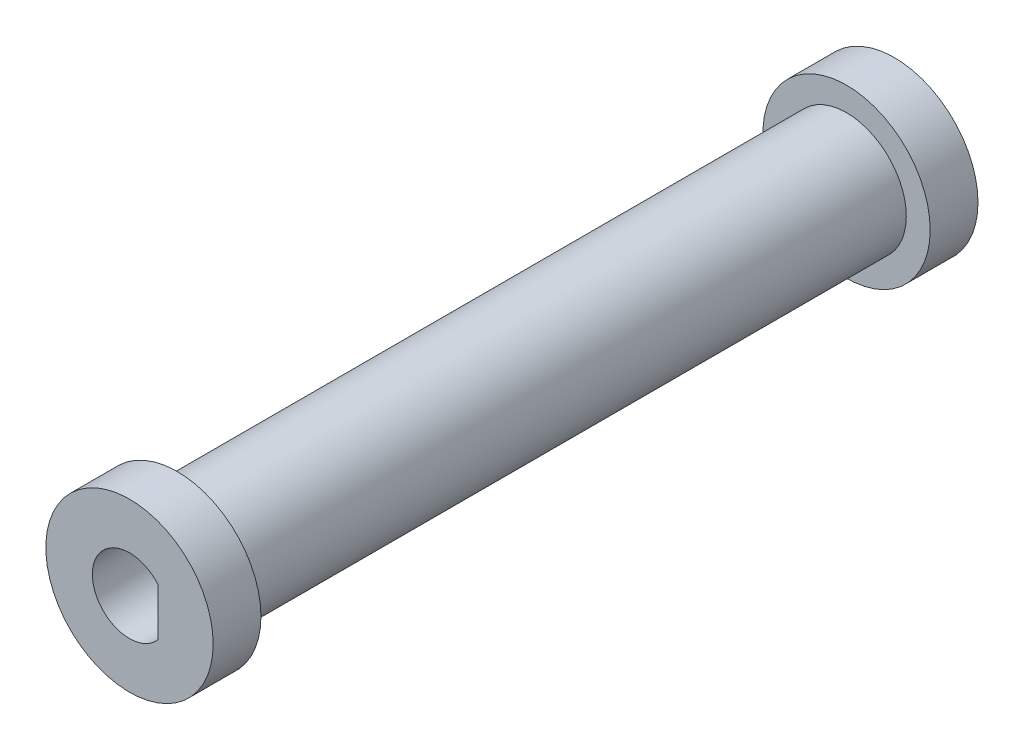
SolidWorks part; units mm, degrees
material "ABS"
ref_plane "Front Plane" through (0, 0, 0) normal (0, 0, 1) x (1, 0, 0)
ref_plane "Top Plane" through (0, 0, 0) normal (0, 1, 0) x (1, 0, 0)
ref_plane "Right Plane" through (0, 0, 0) normal (1, 0, 0) x (0, 0, -1)
sketch "Sketch1" plane through (0, 0, 0) normal (0, 0, 1) x (1, 0, 0)
  circle A0 centre (0, 0) radius 3.175
extrude "Boss-Extrude1" add sketch "Sketch1" along normal blind 35.56 contours A0
ref_plane "Plane1" through (0, 0, 17.78) normal (0, 0, 1) x (1, 0, 0)
sketch "Sketch3" plane through (0, 0, 35.56) normal (0, 0, 1) x (1, 0, 0)
  circle A0 centre (0, 0) radius 4.445
  dimension "D1" = 8.89
extrude "Boss-Extrude2" add sketch "Sketch3" along normal blind 2.54
mirror "Mirror1" about plane through (0, 0, 17.78) normal (0, 0, 1) of "Boss-Extrude2"
sketch "Sketch4" plane through (0, 0, 38.1) normal (0, 0, 1) x (1, 0, 0)
  line L0 (1.525, 0) -> (1.525, 1.255)
  line L1 (1.525, 0) -> (1.525, -1.255)
  arc A0 (1.525, 1.255) -> (1.525, -1.255) centre (0, 0) ccw
  point P6 (0, 0)
  dimension "D1" = 1.255
  dimension "D2" = 1.255
extrude "Cut-Extrude1" cut sketch "Sketch4" against normal blind 10.16 contours A0 L1 L0
